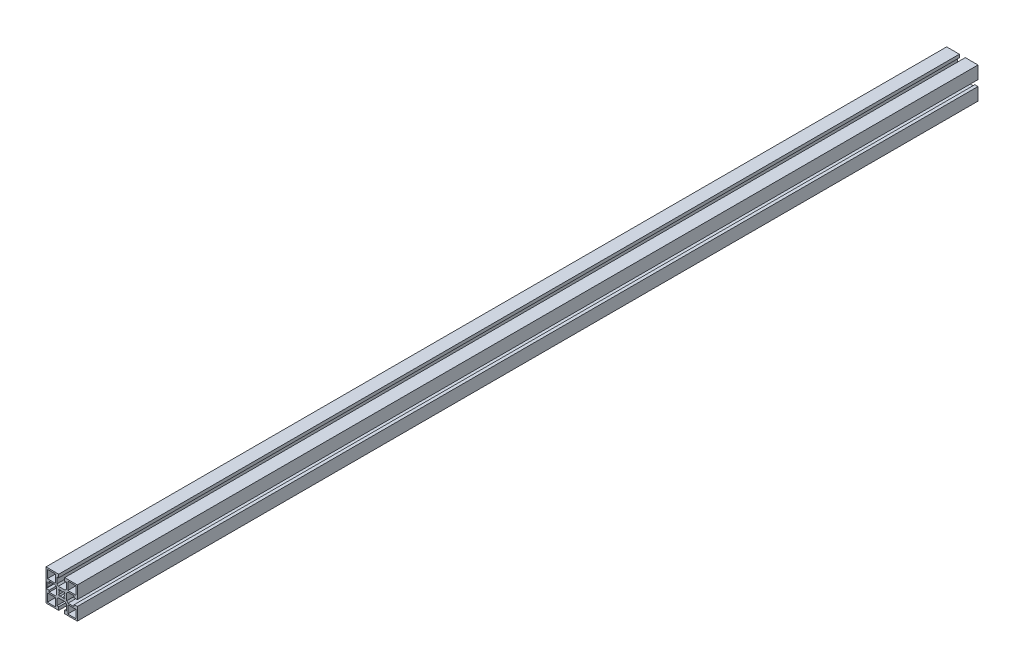
SolidWorks part; units mm, degrees
material "6061 Alloy"
ref_plane "Front Plane" through (0, 0, 0) normal (0, 0, 1) x (1, 0, 0)
ref_plane "Top Plane" through (0, 0, 0) normal (0, 1, 0) x (1, 0, 0)
ref_plane "Right Plane" through (0, 0, 0) normal (1, 0, 0) x (0, 0, -1)
sketch "Sketch1" plane through (0, 0, 0) normal (0, 0, 1) x (1, 0, 0)
  line L0 (-4.2495, 22.1993) -> (-4.2495, 22.4993)
  line L1 (-4.2495, 22.4993) -> (-4.2495, 22.1993)
  line L2 (4.2505, 22.1993) -> (4.2505, 22.4993)
  line L3 (4.2505, 22.4993) -> (4.2505, 22.1993)
  line L4 (-22.1995, 4.2493) -> (-22.4995, 4.2493)
  line L5 (-22.1995, -4.2507) -> (-22.4995, -4.2507)
  line L6 (-4.2495, -22.2007) -> (-4.2495, -22.5007)
  line L7 (4.2505, -22.2007) -> (4.2505, -22.5007)
  line L8 (-22.4995, -22.5007) -> (22.5005, -22.5007)
  line L9 (22.5005, -22.5007) -> (22.5005, 22.4993)
  line L10 (22.5005, 22.4993) -> (-22.4995, 22.4993)
  line L11 (-22.4995, 22.4993) -> (-22.4995, -22.5007)
  line L12 (22.2005, -4.2507) -> (22.5005, -4.2507)
  line L13 (22.2005, 4.2493) -> (22.5005, 4.2493)
  line L24 (-20.4995, -20.5007) -> (-20.4995, -8.8007)
  line L25 (-8.7996, -20.5007) -> (-20.4995, -20.5007)
  line L26 (-8.7996, -8.8007) -> (-8.7996, -20.5007)
  line L27 (-20.4995, -8.8007) -> (-8.7996, -8.8007)
  line L28 (8.8005, -20.5008) -> (8.8005, -8.8008)
  line L29 (20.5005, -20.5008) -> (8.8005, -20.5008)
  line L30 (20.5005, -8.8008) -> (20.5005, -20.5008)
  line L31 (8.8005, -8.8008) -> (20.5005, -8.8008)
  line L32 (20.5006, 8.7993) -> (8.8006, 8.7993)
  line L33 (20.5006, 20.4993) -> (20.5006, 8.7993)
  line L34 (8.8006, 20.4993) -> (20.5006, 20.4993)
  line L35 (8.8006, 8.7993) -> (8.8006, 20.4993)
  line L36 (-8.7995, 20.4993) -> (-8.7995, 8.7993)
  line L37 (-8.7995, 8.7993) -> (-20.4995, 8.7993)
  line L38 (-20.4995, 8.7993) -> (-20.4995, 20.4993)
  line L39 (-20.4995, 20.4993) -> (-8.7995, 20.4993)
  line L54 (-22.1995, -3.9507) -> (-21.7318, -3.483)
  line L55 (-22.1995, -4.2507) -> (-22.1995, -3.9507)
  line L56 (-17.9995, -4.2507) -> (-22.1995, -4.2507)
  line L57 (-17.9995, -6.8007) -> (-17.9995, -4.2507)
  line L58 (-9.1995, -6.8007) -> (-17.9995, -6.8007)
  line L59 (-7.1995, -4.8007) -> (-9.1995, -6.8007)
  line L60 (-7.1995, 4.7993) -> (-7.1995, -4.8007)
  line L61 (-9.1995, 6.7993) -> (-7.1995, 4.7993)
  line L62 (-17.9995, 6.7993) -> (-9.1995, 6.7993)
  line L63 (-17.9995, 4.2493) -> (-17.9995, 6.7993)
  line L64 (-22.1995, 4.2493) -> (-17.9995, 4.2493)
  line L65 (-22.1995, 3.9493) -> (-22.1995, 4.2493)
  line L66 (-21.7317, 3.4815) -> (-22.1995, 3.9493)
  line L67 (-20.9995, -1.7152) -> (-20.9995, 1.7137)
  line L82 (-6.7995, -18.0007) -> (-6.7995, -9.2007)
  line L83 (-4.2495, -18.0007) -> (-6.7995, -18.0007)
  line L84 (-4.2495, -22.2007) -> (-4.2495, -18.0007)
  line L85 (-3.9495, -22.2007) -> (-4.2495, -22.2007)
  line L86 (-3.4817, -21.733) -> (-3.9495, -22.2007)
  line L87 (1.715, -21.0007) -> (-1.7139, -21.0007)
  line L88 (3.9505, -22.2007) -> (3.4828, -21.733)
  line L89 (4.2505, -22.2007) -> (3.9505, -22.2007)
  line L90 (4.2505, -18.0007) -> (4.2505, -22.2007)
  line L91 (6.8005, -18.0007) -> (4.2505, -18.0007)
  line L92 (6.8005, -9.2007) -> (6.8005, -18.0007)
  line L93 (4.8005, -7.2007) -> (6.8005, -9.2007)
  line L94 (-4.7995, -7.2007) -> (4.8005, -7.2007)
  line L95 (-6.7995, -9.2007) -> (-4.7995, -7.2007)
  line L110 (7.2005, -4.8007) -> (7.2005, 4.7993)
  line L111 (9.2005, -6.8007) -> (7.2005, -4.8007)
  line L112 (18.0005, -6.8007) -> (9.2005, -6.8007)
  line L113 (18.0005, -4.2507) -> (18.0005, -6.8007)
  line L114 (22.2005, -4.2507) -> (18.0005, -4.2507)
  line L115 (22.2005, -3.9507) -> (22.2005, -4.2507)
  line L116 (21.7327, -3.4829) -> (22.2005, -3.9507)
  line L117 (21.0005, 1.7138) -> (21.0005, -1.7151)
  line L118 (22.2005, 3.9493) -> (21.7328, 3.4816)
  line L119 (22.2005, 4.2493) -> (22.2005, 3.9493)
  line L120 (18.0005, 4.2493) -> (22.2005, 4.2493)
  line L121 (18.0005, 6.7993) -> (18.0005, 4.2493)
  line L122 (9.2005, 6.7993) -> (18.0005, 6.7993)
  line L123 (7.2005, 4.7993) -> (9.2005, 6.7993)
  line L138 (-4.7995, 7.1993) -> (-6.7995, 9.1993)
  line L139 (4.8005, 7.1993) -> (-4.7995, 7.1993)
  line L140 (6.8005, 9.1993) -> (4.8005, 7.1993)
  line L141 (6.8005, 17.9993) -> (6.8005, 9.1993)
  line L142 (4.2505, 17.9993) -> (6.8005, 17.9993)
  line L143 (4.2505, 22.1993) -> (4.2505, 17.9993)
  line L144 (3.9505, 22.1993) -> (4.2505, 22.1993)
  line L145 (3.4828, 21.7316) -> (3.9505, 22.1993)
  line L146 (-1.7139, 20.9993) -> (1.715, 20.9993)
  line L147 (-3.9495, 22.1993) -> (-3.4817, 21.7315)
  line L148 (-4.2495, 22.1993) -> (-3.9495, 22.1993)
  line L149 (-4.2495, 17.9993) -> (-4.2495, 22.1993)
  line L150 (-6.7995, 17.9993) -> (-4.2495, 17.9993)
  line L151 (-6.7995, 9.1993) -> (-6.7995, 17.9993)
  line L164 (-4.5957, -3.1827) -> (-3.2622, -1.8492)
  line L165 (-3.1815, -4.5969) -> (-4.5957, -3.1827)
  line L166 (-1.848, -3.2635) -> (-3.1815, -4.5969)
  line L167 (3.1825, -4.5969) -> (1.849, -3.2635)
  line L168 (4.5967, -3.1827) -> (3.1825, -4.5969)
  line L169 (3.2633, -1.8492) -> (4.5967, -3.1827)
  line L170 (4.5967, 3.1813) -> (3.2633, 1.8478)
  line L171 (3.1825, 4.5955) -> (4.5967, 3.1813)
  line L172 (1.849, 3.262) -> (3.1825, 4.5955)
  line L173 (-3.1815, 4.5955) -> (-1.848, 3.262)
  line L174 (-4.5957, 3.1813) -> (-3.1815, 4.5955)
  line L175 (-3.2622, 1.8478) -> (-4.5957, 3.1813)
  arc A2 (-21.7318, -3.483) -> (-20.9995, -1.7152) centre (-23.4995, -1.7152) ccw
  arc A3 (-20.9995, 1.7137) -> (-21.7317, 3.4815) centre (-23.4995, 1.7137) ccw
  arc A6 (-1.7139, -21.0007) -> (-3.4817, -21.733) centre (-1.7139, -23.5007) ccw
  arc A7 (3.4828, -21.733) -> (1.715, -21.0007) centre (1.715, -23.5007) ccw
  arc A10 (21.0005, -1.7151) -> (21.7327, -3.4829) centre (23.5005, -1.7151) ccw
  arc A11 (21.7328, 3.4816) -> (21.0005, 1.7138) centre (23.5005, 1.7138) ccw
  arc A14 (1.715, 20.9993) -> (3.4828, 21.7316) centre (1.715, 23.4993) ccw
  arc A15 (-3.4817, 21.7315) -> (-1.7139, 20.9993) centre (-1.7139, 23.4993) ccw
  arc A20 (-1.848, -3.2635) -> (1.849, -3.2635) centre (0.0005, -0.0007) ccw
  arc A21 (3.2633, -1.8492) -> (3.2633, 1.8478) centre (0.0005, -0.0007) ccw
  arc A22 (1.849, 3.262) -> (-1.848, 3.262) centre (0.0005, -0.0007) ccw
  arc A23 (-3.2622, 1.8478) -> (-3.2622, -1.8492) centre (0.0005, -0.0007) ccw
extrude "Boss-Extrude1" add sketch "Sketch1" along normal blind 1292.86 contours L138 L151 L150 L149 L0 L10 L11 L4 L64 L63 L62 L61 L60 L59 L58 L57 L56 L5 L8 L6 L84 L83 L82 L95 L94 L93 L92 L91 L90 L7 L9 L12 L114 L113 L112 L111 L110 L123 L122 L121 L120 L13 L2 L143 L142 L141 L140 | L147 A15 L146 A14 L145 L144 L2 L10 L0 L148 | L67 A3 L66 L65 L4 L11 L5 L55 L54 A2 region at (-4.8859, 20.0993, 0) region at (0.0005, 21.8242, 0) region at (-21.8244, -0.0007, 0)
extrude "Cut-Extrude1" cut sketch "Sketch1<4>" along normal up to next contours L147 A15 L146 A14 L145 L144 L2 L10 L0 L148 region at (0.0005, 21.8242, 0)
sketch "Sketch1<4>" plane through (0, 0, 0) normal (0, 0, 1) x (1, 0, 0) same geometry as "Sketch1"
